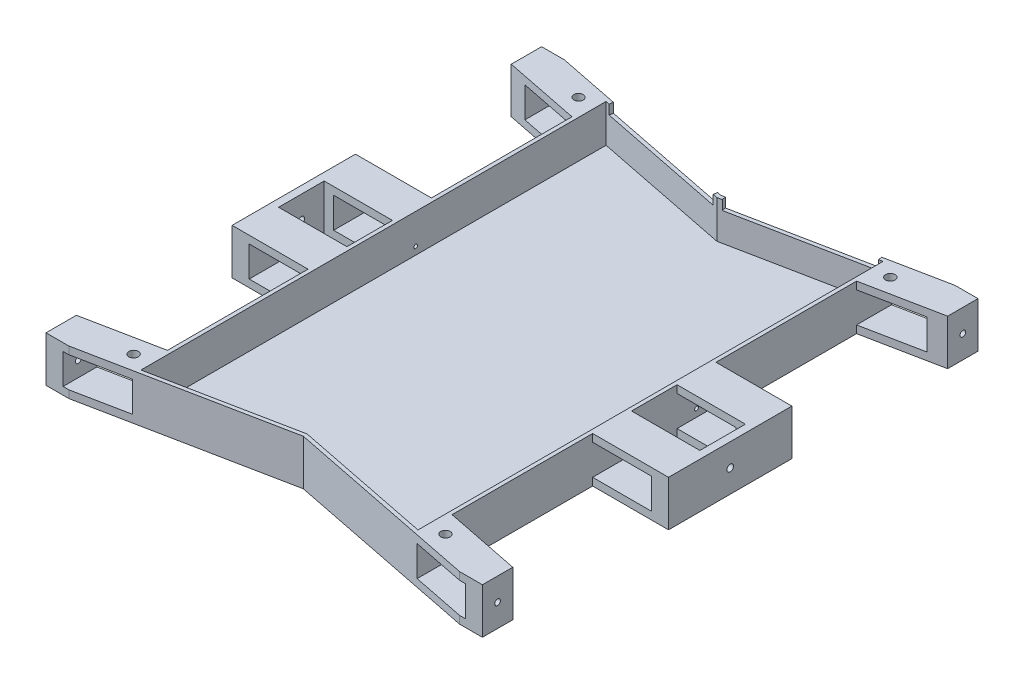
SolidWorks part; units mm, degrees
material "ABS"
ref_plane "Front Plane" through (0, 0, 0) normal (0, 0, 1) x (1, 0, 0)
ref_plane "Top Plane" through (0, 0, 0) normal (0, 1, 0) x (1, 0, 0)
ref_plane "Right Plane" through (0, 0, 0) normal (1, 0, 0) x (0, 0, -1)
sketch "Sketch1" plane through (0, 0, 0) normal (0, 1, 0) x (1, 0, 0)
  line L1 (-55, 0) -> (55, 0) construction
  line L2 (115, 32.5) -> (115, -32.5)
  line L3 (115, -32.5) -> (75, -32.5)
  line L4 (75, -32.5) -> (75, -106.6)
  line L5 (75, -106.6) -> (115, -114.6)
  line L6 (115, -114.6) -> (115, -130.6)
  line L7 (115, -130.6) -> (103, -130.6)
  line L8 (103, -130.6) -> (0, -110)
  line L9 (0, -55) -> (0, 55) construction
  line L11 (-115, 32.5) -> (-115, -32.5)
  line L12 (-115, -32.5) -> (-75, -32.5)
  line L13 (-75, -32.5) -> (-75, -106.6)
  line L14 (-75, -106.6) -> (-115, -114.6)
  line L15 (-115, -114.6) -> (-115, -130.6)
  line L16 (-115, -130.6) -> (-103, -130.6)
  line L17 (-103, -130.6) -> (0, -110)
  line L18 (115, 32.5) -> (75, 32.5)
  line L19 (75, 32.5) -> (75, 106.6)
  line L20 (115, 130.6) -> (103, 130.6)
  line L21 (115, 114.6) -> (115, 130.6)
  line L22 (75, 106.6) -> (115, 114.6)
  line L23 (103, 130.6) -> (0, 110)
  line L24 (-115, 114.6) -> (-115, 130.6)
  line L25 (-115, 130.6) -> (-103, 130.6)
  line L26 (-103, 130.6) -> (0, 110)
  line L27 (-75, 106.6) -> (-115, 114.6)
  line L28 (-115, 32.5) -> (-75, 32.5)
  line L29 (-75, 32.5) -> (-75, 106.6)
  line L30 (75, -106.6) -> (75, -125) construction
  line L32 (-75, -106.6) -> (-75, -125) construction
  line L34 (-75, 106.6) -> (-75, 125) construction
  line L36 (75, 106.6) -> (75, 125) construction
  point P21 (115, 0)
  point P33 (-115, 0)
  dimension "D1" = 250
  dimension "D2" = 220
  dimension "D3" = 150
  dimension "D4" = 16
  dimension "D5" = 12
  dimension "D6" = 65
  dimension "D7" = 40
extrude "Boss-Extrude1" add sketch "Sketch1" along normal blind 12 and the other way blind 12
sketch "Sketch2" plane through (0, 0, 130.6) normal (0, 0, 1) x (1, 0, 0)
  line L0 (-115, -12) -> (-115, 12) construction
  line L1 (-106, -8) -> (106, -8)
  line L2 (-106, -8) -> (-106, 8)
  line L3 (-106, 8) -> (106, 8)
  line L4 (106, -8) -> (106, 8)
  line L5 (115, -12) -> (115, 12) construction
  line L7 (55, 0) -> (-55, 0) construction
  dimension "D1" = 8
  dimension "D2" = 8
  dimension "D3" = 9
  dimension "D4" = 9
extrude "Cut-Extrude1" cut sketch "Sketch2" against normal blind 320
sketch "Sketch4" plane through (0, 12, 0) normal (0, 1, 0) x (1, 0, 0)
  line L0 (-55, 0) -> (55, 0) construction
  line L1 (-111, 12) -> (-75, 12)
  line L2 (-111, 12) -> (-111, -12)
  line L3 (-111, -12) -> (-75, -12)
  line L4 (-75, 12) -> (-75, -12)
  line L5 (-115, 32.5) -> (-115, -32.5) construction
  line L6 (-75, -32.5) -> (-75, -106.6) construction
  line L7 (0, -55) -> (0, 55) construction
  line L8 (111, -12) -> (75, -12)
  line L9 (75, 12) -> (75, -12)
  line L10 (111, 12) -> (75, 12)
  line L11 (111, 12) -> (111, -12)
  dimension "D1" = 12
  dimension "D2" = 12
  dimension "D3" = 4
extrude "Cut-Extrude2" cut sketch "Sketch4" against normal blind 24
sketch "Sketch6" plane through (0, 0, 0) normal (1, 0, 0) x (0, 0, -1)
  line L0 (-114.6, 0) -> (-130.6, 0) construction
  line L1 (114.6, 0) -> (130.6, 0) construction
  circle A0 centre (-122.6, 0) radius 1.5
  circle A1 centre (122.6, 0) radius 1.5
  point P6 (-122.6, 0)
  point P10 (122.6, 0)
  dimension "D1" = 3
extrude "Cut-Extrude3" cut sketch "Sketch6" against normal through all both and the other way through all
sketch "Sketch7" plane through (115, 0, 0) normal (1, 0, 0) x (0, 0, -1)
  circle A0 centre (0, 0) radius 1.75
  dimension "D1" = 3.5
extrude "Cut-Extrude4" cut sketch "Sketch7" against normal up to surface (230 mm away) up to face at (-115, 0, 0)
sketch "Sketch8" plane through (0, 12, 0) normal (0, 1, 0) x (1, 0, 0)
  line L0 (0, 110) -> (0, -110) construction
  line L1 (106, -12) -> (106, 12) construction
  line L2 (106, 8) -> (94, 8)
  line L3 (106, 8) -> (106, -8)
  line L4 (106, -8) -> (94, -8)
  line L5 (94, 8) -> (94, -8)
  line L6 (-106, 0) -> (115, 0) construction
  line L7 (-106, 12) -> (-106, -12) construction
  line L8 (115, -32.5) -> (115, 32.5) construction
  line L9 (-106, -8) -> (-94, -8)
  line L10 (-94, 8) -> (-94, -8)
  line L11 (-106, 8) -> (-94, 8)
  line L12 (-106, 8) -> (-106, -8)
  point P16 (94, 0)
  dimension "D1" = 16
  dimension "D2" = 12
extrude "Cut-Extrude5" [suppressed] cut sketch "Sketch8" against normal up to surface (5 mm away) up to face at (0, 8, 0)
sketch "Sketch11" plane through (0, 12, 0) normal (0, 1, 0) x (1, 0, 0)
  line L0 (-75, -125) -> (-75, 125)
  line L1 (-103, -130.6) -> (0, -110) construction
  line L2 (0, 110) -> (-103, 130.6) construction
  line L3 (75, 125) -> (75, -125)
  line L4 (103, 130.6) -> (0, 110) construction
  line L5 (0, -110) -> (103, -130.6) construction
  line L6 (75, 32.5) -> (75, 106.6) construction
  line L7 (-75, 106.6) -> (-75, 32.5) construction
  line L8 (0, -110) -> (75, -125)
  line L9 (-75, -125) -> (0, -110)
  line L10 (0, 110) -> (-75, 125)
  line L11 (75, 125) -> (0, 110)
extrude "Cut-Extrude7" cut sketch "Sketch11" against normal up to surface (4 mm away) up to face at (0, 8, 0)
sketch "Sketch12" plane through (0, -8, 0) normal (0, 1, 0) x (1, 0, 0)
  line L0 (-75, 125) -> (-75, -125)
  line L1 (-103, -130.6) -> (0, -110) construction
  line L2 (75, 125) -> (75, -125)
  line L3 (-75, -125) -> (0, -110)
  line L4 (0, -110) -> (75, -125)
  line L5 (-75, 125) -> (0, 110)
  line L6 (0, 110) -> (75, 125)
  line L7 (0, 107.9604) -> (73, 122.5604)
  line L8 (73, 122.5604) -> (73, -122.5604)
  line L9 (0, -107.9604) -> (73, -122.5604)
  line L10 (-73, -122.5604) -> (0, -107.9604)
  line L11 (-73, 122.5604) -> (-73, -122.5604)
  line L12 (-73, 122.5604) -> (0, 107.9604)
  dimension "D1" = 2
extrude "Boss-Extrude2" add sketch "Sketch12" along normal blind 20
sketch "Sketch14" plane through (0, 12, 0) normal (0, 1, 0) x (1, 0, 0)
  line L0 (0, 110) -> (0, -110) construction
  line L1 (75, 0) -> (-75, 0) construction
  line L2 (75, -12) -> (75, 12) construction
  line L3 (-75, 12) -> (-75, -12) construction
  line L4 (-83.9461, 108.3892) -> (-80.4076, 126.0815) construction
  line L5 (-115, 114.6) -> (-75, 106.6) construction
  line L6 (0, 110) -> (-103, 130.6) construction
  circle A0 centre (-82.1768, 117.2354) radius 2.5
  circle A1 centre (82.1768, 117.2354) radius 2.5
  circle A2 centre (82.1768, -117.2354) radius 2.5
  circle A3 centre (-82.1768, -117.2354) radius 2.5
  dimension "D2" = 5
  dimension "D1" = 82
extrude "Cut-Extrude8" cut sketch "Sketch14" against normal up to next
sketch "Sketch15" plane through (0, 12, 0) normal (0, 1, 0) x (1, 0, 0)
  line L0 (-71.0388, 122.1682) -> (-70.6466, 124.1293)
  line L1 (0, 110) -> (-103, 130.6) construction
  line L2 (0, 107.9604) -> (-73, 122.5604) construction
  line L3 (-2.3982, 108.44) -> (-71.0388, 122.1682)
  line L4 (-2.006, 110.4012) -> (-70.6466, 124.1293)
  line L5 (73, 122.5604) -> (0, 107.9604) construction
  line L6 (103, 130.6) -> (0, 110) construction
  line L7 (71.0388, 122.1682) -> (2.3982, 108.44)
  line L8 (70.6466, 124.1293) -> (2.006, 110.4012)
  line L10 (-2.3982, 108.44) -> (-2.006, 110.4012)
  line L11 (2.3982, 108.44) -> (2.006, 110.4012)
  line L12 (70.6466, 124.1293) -> (71.0388, 122.1682)
  dimension "D1" = 70
  dimension "D2" = 70
  dimension "D3" = 2
  dimension "D4" = 2
extrude "Cut-Extrude9" cut sketch "Sketch15" against normal blind 5
sketch "Sketch16" plane through (75, 0, 0) normal (1, 0, 0) x (0, 0, -1)
  line L0 (22.25, 8) -> (22.25, -8) construction
  line L1 (32.5, 8) -> (12, 8) construction
  line L2 (12, -8) -> (32.5, -8) construction
  circle A0 centre (22.25, -4) radius 1
  point P9 (22.25, 0)
  dimension "D2" = 2
  dimension "D1" = 4
extrude "Cut-Extrude10" cut sketch "Sketch16" against normal up to surface (150 mm away) up to face at (-75, 0, 0)
equation "\"A\"= 4"
equation "\"D1@Boss-Extrude1\"=3*\"A\""
equation "\"D2@Boss-Extrude1\"=3*\"A\""
equation "\"D1@Sketch2\"=2*\"A\""
equation "\"D2@Sketch2\"=2*\"A\""
equation "\"D1@Sketch4\"=3*\"A\""
equation "\"D2@Sketch4\"=3*\"A\""
equation "\"D3@Sketch4\"=\"A\""
equation "\"D1@Cut-Extrude2\"=6*\"A\""
equation "\"D1@Cut-Extrude1\"=80*\"A\""
